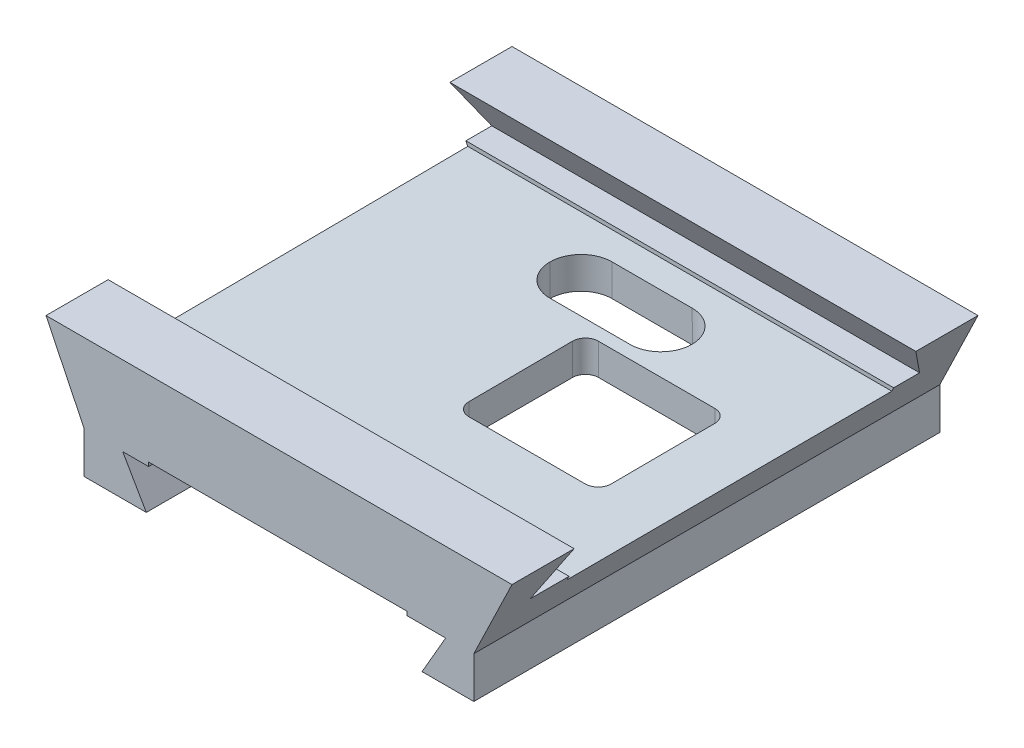
SolidWorks part; units mm, degrees
ref_plane "Front Plane" through (0, 0, 0) normal (0, 0, 1) x (1, 0, 0)
ref_plane "Top Plane" through (0, 0, 0) normal (0, 1, 0) x (1, 0, 0)
ref_plane "Right Plane" through (0, 0, 0) normal (1, 0, 0) x (0, 0, -1)
sketch "Sketch1" plane through (0, 0, 0) normal (0, 0, 1) x (1, 0, 0)
  line L0 (-75.25, 0) -> (75.25, 0)
  line L1 (75.25, 0) -> (75.25, 16)
  line L2 (75.25, 16) -> (90, 46.5)
  line L3 (-75.25, 0) -> (-75.25, 16)
  line L4 (-75.25, 16) -> (-90, 46.5)
  line L5 (-90, 46.5) -> (90, 46.5)
  dimension "D1" = 75.25
  dimension "D2" = 75.25
  dimension "D3" = 16
  dimension "D4" = 16
  dimension "D5" = 46.5
  dimension "D6" = 90
  dimension "D7" = 46.5
  dimension "D8" = 90
extrude "Boss-Extrude1" add sketch "Sketch1" along normal blind 180
sketch "Sketch2" plane through (0, 0, 180) normal (0, 0, 1) x (1, 0, 0)
  line L0 (-51.25, 0) -> (-60.3721, 15.8)
  line L1 (-75.25, 0) -> (75.25, 0) construction
  line L2 (-60.3721, 15.8) -> (-50.3721, 15.8)
  line L3 (-50.3721, 15.8) -> (-50.3721, 17.3)
  line L4 (55.25, 0) -> (64.3721, 15.8)
  line L5 (64.3721, 15.8) -> (49.3721, 15.8)
  line L6 (49.3721, 15.8) -> (49.3721, 17.3)
  line L7 (-50.3721, 17.3) -> (49.3721, 17.3)
  line L8 (-51.25, 0) -> (55.25, 0)
  dimension "D1" = 24
  dimension "D2" = 15.8
  dimension "D3" = 60
  dimension "D4" = 10
  dimension "D5" = 1.5
  dimension "D6" = 20
  dimension "D7" = 60
  dimension "D8" = 15.8
  dimension "D9" = 15
extrude "Cut-Extrude1" cut sketch "Sketch2" against normal through all
sketch "Sketch3" plane through (0, 0, 180) normal (0, 0, 1) x (1, 0, 0)
  line L0 (90, 46.5) -> (75.25, 16)
  line L1 (75.25, 16) -> (90, 16)
  line L2 (90, 16) -> (90, 46.5)
extrude "Boss-Extrude2" add sketch "Sketch3" against normal blind 175 separate body
sketch "Sketch5" plane through (90, 0, 0) normal (1, 0, 0) x (0, 0, -1)
  line L0 (-156, 46.5) -> (-165.2376, 30.5)
  line L1 (-5, 46.5) -> (-180, 46.5) construction
  line L2 (-165.2376, 30.5) -> (-150.2376, 30.5)
  line L3 (-150.2376, 30.5) -> (-150.2376, 29)
  line L4 (-180, 46.5) -> (0, 46.5) construction
  line L5 (-24, 46.5) -> (-15.1856, 31.233)
  line L6 (-15.1856, 31.233) -> (-25.1856, 31.233)
  line L7 (-25.1856, 31.233) -> (-25.1856, 29.733)
  line L8 (0, 16) -> (0, 46.5) construction
  line L9 (-150.2376, 29) -> (-25.1856, 29.733)
  line L10 (-156, 46.5) -> (-24, 46.5)
  dimension "D1" = 24
  dimension "D2" = 16
  dimension "D3" = 15
  dimension "D4" = 1.5
  dimension "D5" = 24
  dimension "D6" = 60
  dimension "D7" = 60
  dimension "D8" = 10
  dimension "D9" = 1.5
extrude "Cut-Extrude5" cut sketch "Sketch5" against normal blind 180
sketch "Sketch6" plane through (0, 0, 180) normal (0, 0, 1) x (1, 0, 0)
  line L0 (75.25, 16) -> (90, 46.5)
  line L1 (90, 46.5) -> (90, 16)
  line L2 (90, 16) -> (75.25, 16)
extrude "Cut-Extrude6" cut sketch "Sketch6" against normal blind 180
sketch "Sketch7" plane through (0, 29.8795, 0.1751) normal (0, 1, 0.0059) x (1, 0, 0)
  line L0 (90, 0.2725) -> (-90, 0.2725) construction
  line L1 (-27.5, -59.7275) -> (27.5, -59.7275)
  line L2 (-27.5, -59.7275) -> (-27.5, -35.7275)
  line L3 (-27.5, -35.7275) -> (27.5, -35.7275)
  line L4 (27.5, -59.7275) -> (27.5, -35.7275)
  dimension "D1" = 27.5
  dimension "D2" = 27.5
  dimension "D3" = 36
  dimension "D4" = 24
extrude "Cut-Extrude7" cut sketch "Sketch7" against normal blind 180
sketch "Sketch8" plane through (0, 29.8795, 0.1751) normal (0, 1, 0.0059) x (1, 0, 0)
  line L0 (90, -179.7244) -> (-90, -179.7244) construction
  line L1 (3.227, -114.7244) -> (58.227, -114.7244)
  line L2 (3.227, -114.7244) -> (3.227, -64.7244)
  line L3 (3.227, -64.7244) -> (58.227, -64.7244)
  line L4 (58.227, -114.7244) -> (58.227, -64.7244)
  dimension "D1" = 50
  dimension "D2" = 55
  dimension "D3" = 65
extrude "Cut-Extrude8" cut sketch "Sketch8" against normal blind 180
fillet "Fillet1" radius 12 1 edges at (-27.5, 23.4147, 59.8657)
fillet "Fillet2" radius 12 1 edges at (-27.5, 23.4851, 35.8657)
fillet "Fillet3" radius 12 1 edges at (27.5, 23.4147, 59.8657)
fillet "Fillet4" radius 12 1 edges at (27.5, 23.4851, 35.8657)
fillet "Fillet5" radius 5 1 edges at (58.227, 22.6501, 64.8582)
fillet "Fillet6" radius 5 1 edges at (3.227, 23.4001, 64.8626)
fillet "Fillet7" radius 5 1 edges at (3.227, 23.2536, 114.8626)
fillet "Fillet8" radius 5 1 edges at (58.227, 22.5036, 114.8582)
